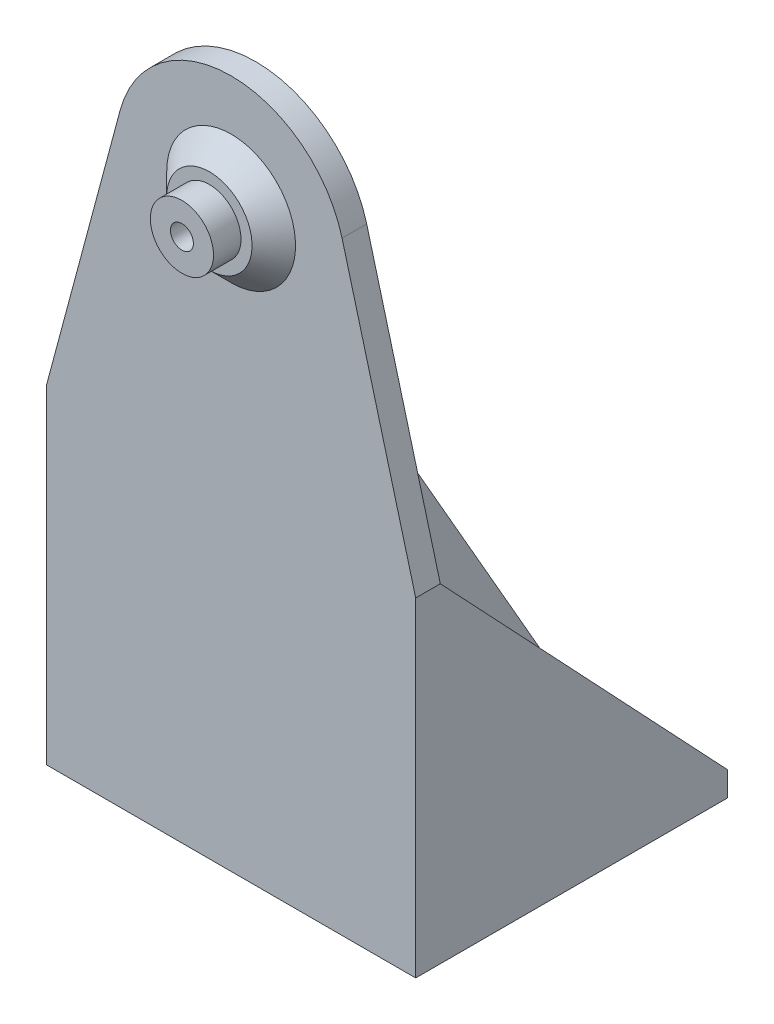
SolidWorks part; units mm, degrees
ref_plane "前视基准面" through (0, 0, 0) normal (0, 0, 1) x (1, 0, 0)
ref_plane "上视基准面" through (0, 0, 0) normal (0, 1, 0) x (1, 0, 0)
ref_plane "右视基准面" through (0, 0, 0) normal (1, 0, 0) x (0, 0, -1)
other "Configuration Table"
sketch "草图1" plane through (0, 0, 0) normal (0, 0, 1) x (1, 0, 0)
  circle A0 centre (0, 0) radius 1.4
  circle A1 centre (0, 0) radius 3.85
  dimension "D1" = 7.7
  dimension "D2" = 2.8
extrude "凸台-拉伸1" add sketch "草图1" against normal blind 3.35 contours A0 | A1
ref_plane "基准面1" through (0, 0, -3.35) normal (0, 0, -1) x (-1, 0, 0)
sketch "草图2" plane through (0, 0, -3.35) normal (0, 0, -1) x (-1, 0, 0)
  circle A0 centre (0, 0) radius 5.2
  dimension "D1" = 10.4
ref_plane "基准面2" through (0, 0, -6) normal (0, 0, -1) x (-1, 0, 0)
sketch "草图3" plane through (0, 0, -6) normal (0, 0, -1) x (-1, 0, 0)
  circle A0 centre (0, 0) radius 7.85
  dimension "D1" = 15.7
loft "放样1" add profiles "草图3", "草图2" connector at (6.7593, 3.9917, -6) connector at (4.4775, 2.6442, -3.35)
sketch "草图6" plane through (0, 0, -6) normal (0, 0, -1) x (-1, 0, 0)
  line L1 (0, 0) -> (0, 14) construction
  line L5 (-22.4988, -29.8748) -> (-22.4988, -69.9948)
  line L6 (22.4988, -29.8748) -> (22.4988, -69.9948)
  line L7 (-22.4988, -69.9948) -> (22.4988, -69.9948)
  line L8 (13.523, 3.6235) -> (22.4988, -29.8748)
  line L9 (-13.523, 3.6235) -> (-22.4988, -29.8748)
  arc A0 (-13.523, 3.6235) -> (13.523, 3.6235) centre (0, 0) cw
  dimension "D1" = 14
  dimension "D2" = 14
  dimension "D3" = 34.68
  dimension "D7" = 34.68
  dimension "D8" = 40.12
  dimension "D9" = 40.12
extrude "凸台-拉伸2" add sketch "草图6" along normal blind 3
sketch "草图7" plane through (0, 0, -9) normal (0, 0, -1) x (-1, 0, 0)
  circle A1 centre (0, 0) radius 1.4
  dimension "D1" = 2.8
extrude "切除-拉伸1" cut sketch "草图7" against normal blind 23.35
sketch "草图11" plane through (0, 0, -9) normal (0, 0, -1) x (-1, 0, 0)
  line L0 (-22.4988, -66.9948) -> (22.4988, -66.9948)
  line L1 (-22.4988, -29.8748) -> (-22.4988, -69.9948) construction
  line L2 (22.4988, -69.9948) -> (22.4988, -29.8748) construction
  line L3 (-22.4988, -69.9948) -> (22.4988, -69.9948) construction
  line L9 (-13.523, 3.6235) -> (-22.4988, -29.8748)
  line L10 (-22.4988, -29.8748) -> (-22.4988, -69.9948)
  line L11 (-22.4988, -69.9948) -> (22.4988, -69.9948)
  line L12 (22.4988, -69.9948) -> (22.4988, -29.8748)
  line L13 (22.4988, -29.8748) -> (13.523, 3.6235)
  line L15 (-22.4988, -66.9948) -> (-22.4988, -69.9948)
  line L16 (-22.4988, -69.9948) -> (22.4988, -69.9948)
  line L17 (22.4988, -69.9948) -> (22.4988, -66.9948)
  arc A1 (13.523, 3.6235) -> (-13.523, 3.6235) centre (0, 0) ccw
  dimension "D1" = 3
  dimension "D2" = 0
extrude "凸台-拉伸3" add sketch "草图11" along normal blind 35
ref_plane "基准面3" through (0, -66.9948, 0) normal (0, 1, 0) x (1, 0, 0)
sketch "草图14" plane through (0, -66.9948, 0) normal (0, 1, 0) x (1, 0, 0)
  line L0 (-14.0797, 35) -> (-14.0797, 18)
  line L1 (-22.4988, 44) -> (-22.4988, 9) construction
  line L2 (-22.4988, 44) -> (22.4988, 44) construction
  line L3 (-14.0797, 35) -> (-12.4814, 35) construction
  line L4 (-10.8831, 18) -> (-10.8831, 35)
  line L5 (0, 26.5) -> (0, 55.1831) construction
  line L6 (0, 55.1831) -> (0, -7.3456) construction
  line L9 (22.4988, 26.5) -> (-22.4988, 26.5) construction
  line L10 (22.4988, 44) -> (22.4988, 9) construction
  line L11 (10.8831, 35) -> (10.8831, 18)
  line L12 (14.0797, 18) -> (14.0797, 35)
  arc A0 (-14.0797, 35) -> (-10.8831, 35) centre (-12.4814, 35) cw
  arc A1 (14.0797, 35) -> (10.8831, 35) centre (12.4814, 35) ccw
  arc A4 (14.0797, 18) -> (10.8831, 18) centre (12.4814, 18) cw
  arc A5 (-14.0797, 18) -> (-10.8831, 18) centre (-12.4814, 18) ccw
  dimension "D1" = 12.4814
  dimension "D3" = 9
  dimension "D4" = 1.5983
extrude "切除-拉伸4" cut sketch "草图14" against normal blind 35
ref_plane "基准面4" through (22.4988, 0, 0) normal (1, 0, 0) x (0, 0, -1)
sketch "草图15" plane through (22.4988, 0, 0) normal (1, 0, 0) x (0, 0, -1)
  line L0 (9, -29.8748) -> (44, -66.9948)
  line L7 (6, -29.8748) -> (6, -69.9948)
  line L8 (6, -69.9948) -> (44, -69.9948)
  line L9 (44, -69.9948) -> (44, -66.9948)
  line L10 (44, -66.9948) -> (9, -66.9948)
  line L11 (9, -66.9948) -> (9, -29.8748)
  line L12 (9, -29.8748) -> (6, -29.8748)
  line L13 (6, -29.8748) -> (6, -69.9948)
  line L14 (6, -69.9948) -> (44, -69.9948)
  line L15 (44, -69.9948) -> (44, -66.9948)
  line L18 (9, -29.8748) -> (6, -29.8748)
  dimension "D1" = 0
extrude "凸台-拉伸4" add sketch "草图15" against normal blind 3
ref_plane "基准面5" through (0, 0, 0) normal (1, 0, 0) x (0, 0, -1)
mirror "镜向1" about plane through (0, 0, 0) normal (1, 0, 0) of "凸台-拉伸4"
sketch "草图19" plane through (0, 0, 0) normal (1, 0, 0) x (0, 0, -1)
  line L0 (44, -66.9948) -> (9, -6.0215)
  line L1 (9, 3.6235) -> (9, -29.8748) construction
  line L2 (9, -6.0215) -> (9, -66.9948)
  line L3 (55.1831, -66.9948) -> (-7.3456, -66.9948) construction
  line L4 (9, -66.9948) -> (44, -66.9948)
  dimension "D1" = 70.3047
extrude "凸台-拉伸5" add sketch "草图19" along normal blind 1.5 and the other way blind 1.5
